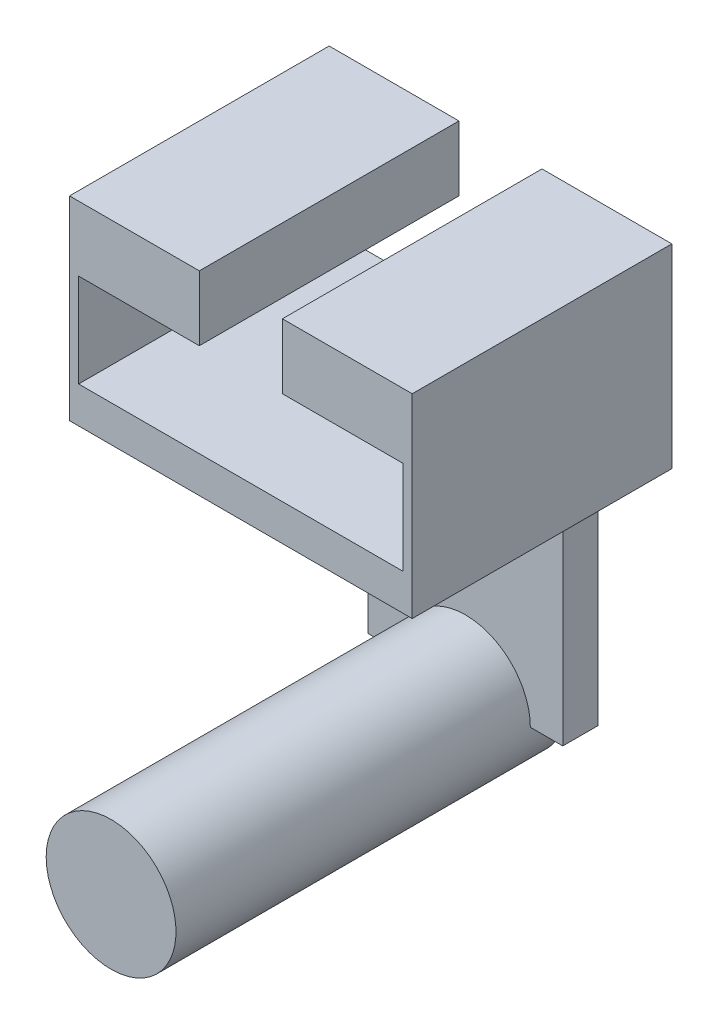
SolidWorks part; units mm, degrees
material "6061-T6 (SS)"
ref_plane "Front Plane" through (0, 0, 0) normal (0, 0, 1) x (1, 0, 0)
ref_plane "Top Plane" through (0, 0, 0) normal (0, 1, 0) x (1, 0, 0)
ref_plane "Right Plane" through (0, 0, 0) normal (1, 0, 0) x (0, 0, -1)
sketch "Sketch3" plane through (0, 0, 0) normal (0, 0, 1) x (1, 0, 0)
  line L0 (19.05, 50.8) -> (19.05, 0) construction
  line L1 (0, 0) -> (6.35, 0)
  line L2 (0, 0) -> (0, 50.8)
  line L3 (0, 50.8) -> (38.1, 50.8)
  line L4 (38.1, 0) -> (38.1, 50.8)
  line L5 (31.75, 0) -> (38.1, 0)
  arc A0 (31.75, 0) -> (6.35, 0) centre (19.05, 0) ccw
  arc A1 (6.35, 0) -> (31.75, 0) centre (19.05, 0) cw
  dimension "D1" = 50.8
  dimension "D2" = 38.1
extrude "Boss-Extrude4" add sketch "Sketch3" along normal blind 6.858 contours A1 L5 L4 L3 L2 L1
sketch "Sketch7" plane through (0, 0, 0) normal (0, 0, -1) x (-1, 0, 0)
  line L0 (-38.1, 0) -> (0, 0) construction
  line L1 (-19.05, 50.8) -> (-19.05, 0) construction
  line L2 (0, 50.8) -> (-38.1, 50.8) construction
  circle A0 centre (-19.05, 0) radius 12.7
  dimension "D1" = 25.4
extrude "Boss-Extrude5" add sketch "Sketch7" against normal blind 76.2
sketch "Sketch9" plane through (0, 50.8, 0) normal (0, 1, 0) x (1, 0, 0)
  line L0 (19.05, 0) -> (19.05, -6.858) construction
  line L1 (0, 0) -> (38.1, 0) construction
  line L2 (0, -6.858) -> (38.1, -6.858) construction
  line L3 (0, -3.429) -> (19.05, -3.429) construction
  line L4 (0, -6.858) -> (0, 0) construction
  line L5 (19.05, -50.8) -> (19.05, 0) construction
  line L6 (-12.7, 0) -> (50.8, 0)
  line L7 (-12.7, 0) -> (-12.7, -50.8)
  line L8 (-12.7, -50.8) -> (50.8, -50.8)
  line L9 (50.8, 0) -> (50.8, -50.8)
  dimension "D1" = 63.5
  dimension "D2" = 50.8
  dimension "D3" = 0
extrude "Boss-Extrude6" add sketch "Sketch9" along normal blind 7.112
sketch "Sketch11" plane through (50.8, 0, 0) normal (1, 0, 0) x (0, 0, -1)
  line L0 (-25.4, 57.912) -> (-25.4, 50.8) construction
  line L1 (-50.8, 57.912) -> (0, 57.912) construction
  line L2 (-50.8, 50.8) -> (0, 50.8) construction
  line L3 (-50.8, 54.356) -> (-25.4, 54.356) construction
  line L4 (-50.8, 57.912) -> (-50.8, 50.8) construction
  line L5 (-25.4, 50.8) -> (-25.4, 88.9) construction
  line L6 (-50.8, 88.9) -> (0, 88.9)
  line L7 (-50.8, 88.9) -> (-50.8, 50.8)
  line L8 (-50.8, 50.8) -> (0, 50.8)
  line L9 (0, 88.9) -> (0, 50.8)
  dimension "D1" = 38.1
  dimension "D2" = 50.8
extrude "Boss-Extrude7" add sketch "Sketch11" along normal blind 1.778
sketch "Sketch12" plane through (-12.7, 0, 0) normal (-1, 0, 0) x (0, 0, 1)
  line L6 (0, 88.9) -> (50.8, 88.9)
  line L7 (0, 88.9) -> (0, 50.8)
  line L8 (0, 50.8) -> (50.8, 50.8)
  line L9 (50.8, 88.9) -> (50.8, 50.8)
  dimension "D1" = 38.1
  dimension "D2" = 50.8
extrude "Boss-Extrude8" add sketch "Sketch12" along normal blind 1.778
sketch "Sketch14" plane through (0, 88.9, 0) normal (0, 1, 0) x (1, 0, 0)
  line L1 (52.578, 0) -> (27.178, 0)
  line L2 (52.578, 0) -> (52.578, -50.8)
  line L3 (52.578, -50.8) -> (27.178, -50.8)
  line L4 (27.178, 0) -> (27.178, -50.8)
  dimension "D1" = 50.8
  dimension "D2" = 25.4
extrude "Boss-Extrude9" add sketch "Sketch14" against normal blind 12.7
sketch "Sketch15" plane through (0, 88.9, 0) normal (0, 1, 0) x (1, 0, 0)
  line L1 (-14.478, 0) -> (10.922, 0)
  line L2 (-14.478, 0) -> (-14.478, -50.8)
  line L3 (-14.478, -50.8) -> (10.922, -50.8)
  line L4 (10.922, 0) -> (10.922, -50.8)
  dimension "D1" = 50.8
  dimension "D2" = 25.4
extrude "Boss-Extrude10" add sketch "Sketch15" against normal blind 12.7
equation "\"ShaftL\"= 3in"
equation "\"ShaftD\"= 1in"
equation "\"BWidth\"= 1.5in"
equation "\"BLength\"= 2in"
equation "\"BThickness\"= 0.27in"
equation "\"CLegth\"= 2.5in"
equation "\"CWidth\"= 2in"
equation "\"CHeight\"= 0.28in"
equation "\"DLength\"= 2in"
equation "\"DWidth\"= 1.498in"
equation "\"DThickness\"= 0.07in"
equation "\"ELength\"= 2in"
equation "\"EWidth\"= 0.9990"
equation "\"EHeight\"= 0.5in"
